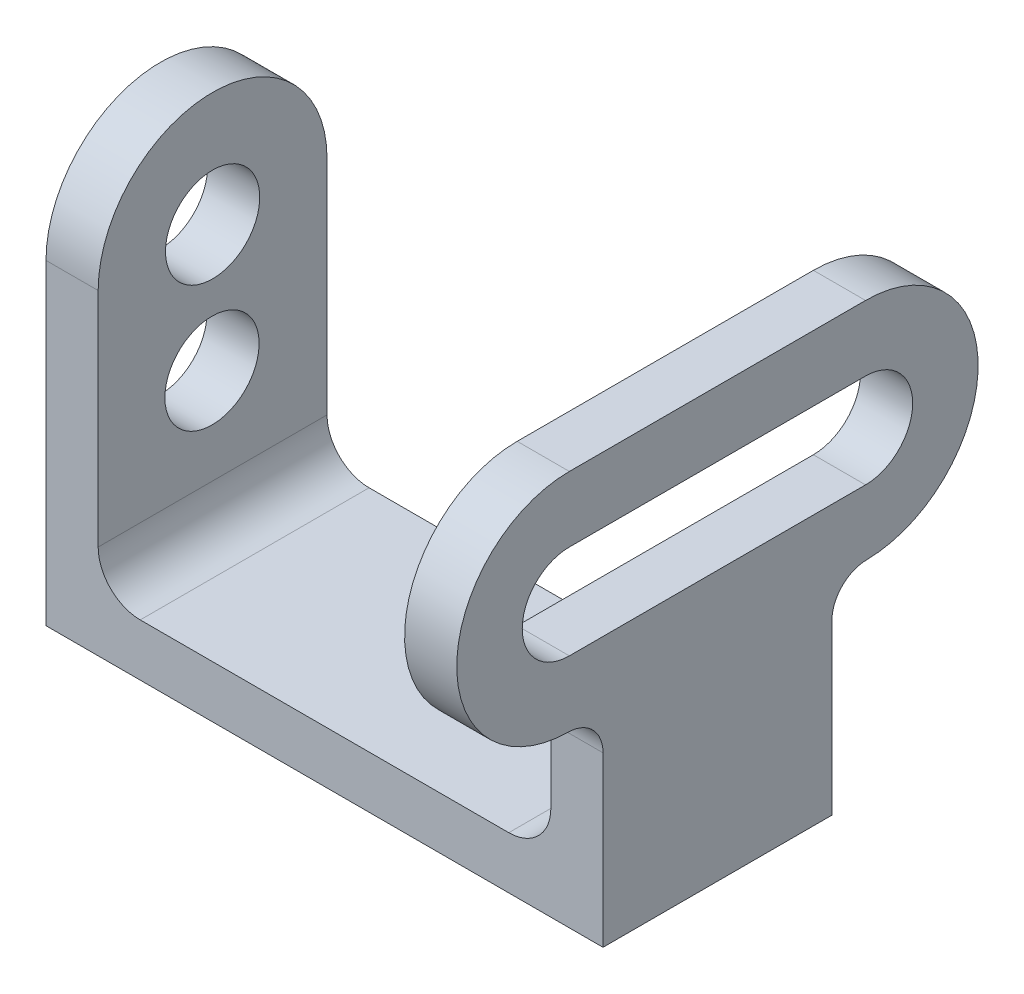
SolidWorks part; units mm, degrees
ref_plane "Front Plane" through (0, 0, 0) normal (0, 0, 1) x (1, 0, 0)
ref_plane "Top Plane" through (0, 0, 0) normal (0, 1, 0) x (1, 0, 0)
ref_plane "Right Plane" through (0, 0, 0) normal (1, 0, 0) x (0, 0, -1)
sketch "Sketch1" plane through (0, 0, 0) normal (0, 0, 1) x (1, 0, 0)
  line L0 (-66.2224, 33.9296) -> (-58.3484, 33.9296)
  line L1 (-58.3484, 33.9296) -> (-58.3484, -5.9484)
  line L2 (-58.3484, -5.9484) -> (9.9776, -5.9484)
  line L3 (9.9776, -5.9484) -> (9.9776, 33.9296)
  line L4 (9.9776, 33.9296) -> (17.8516, 33.9296)
  line L5 (17.8516, 33.9296) -> (17.8516, -13.8224)
  line L6 (17.8516, -13.8224) -> (-66.2224, -13.8224)
  line L7 (-66.2224, -13.8224) -> (-66.2224, 33.9296)
  dimension "D1" = 7.874
  dimension "D2" = 84.074
  dimension "D3" = 47.752
  dimension "D4" = 7.874
extrude "Boss-Extrude1" add sketch "Sketch1" against normal blind 34.544
sketch "Sketch2" plane through (-66.2224, 0, 0) normal (-1, 0, 0) x (0, 0, 1)
  line L0 (-34.544, 33.9296) -> (0, 33.9296) construction
  circle A0 centre (-17.272, 33.9296) radius 17.272
  circle A1 centre (-17.272, 33.9296) radius 7.112
  circle A2 centre (-17.1815, 14.8796) radius 7.112
  line M5 (0, 33.9296) -> (-34.544, 33.9296)
  dimension "D1" = 14.224
  dimension "D2" = 19.05
extrude "Cut-Extrude1" cut sketch "Sketch2" against normal up to surface (7.874 mm away) contours A1 M5 | A0 A2 | A0 A2 region at (-66.2224, 13.0217, -17.1727) region at (-66.2224, 19.1025, -17.2016) region at (-66.2224, 30.9112, -17.272) up to face at (-58.3484, 13.9906, -17.272)
extrude "Boss-Extrude2" add sketch "Sketch2<3>" against normal up to surface (7.874 mm away) contours A1 A0 M5 region at (-66.2224, 42.1404, -17.272) up to face at (-58.3484, 19.4516, -17.272)
sketch "Sketch2<3>" plane through (-66.2224, 0, 0) normal (-1, 0, 0) x (0, 0, 1) same geometry as "Sketch2"
sketch "Sketch3" plane through (17.8516, 0, 0) normal (1, 0, 0) x (0, 0, -1)
  line L0 (-5.08, 33.9296) -> (39.624, 33.9296) construction
  line L1 (34.544, 33.9296) -> (0, 33.9296) construction
  line L2 (-5.08, 50.9242) -> (39.624, 50.9242)
  line L3 (-5.08, 16.935) -> (39.624, 16.935)
  line L4 (-5.08, 33.9296) -> (39.624, 33.9296) construction
  line L5 (-5.08, 41.0416) -> (39.624, 41.0416)
  line L6 (-5.08, 26.8176) -> (39.624, 26.8176)
  line L7 (0, -13.8224) -> (0, 33.9296) construction
  line L8 (34.544, -13.8224) -> (34.544, 33.9296) construction
  arc A0 (-5.08, 50.9242) -> (-5.08, 16.935) centre (-5.08, 33.9296) ccw
  arc A1 (39.624, 16.935) -> (39.624, 50.9242) centre (39.624, 33.9296) ccw
  arc A2 (-5.08, 41.0416) -> (-5.08, 26.8176) centre (-5.08, 33.9296) ccw
  arc A3 (39.624, 26.8176) -> (39.624, 41.0416) centre (39.624, 33.9296) ccw
  arc A4 (0, 11.6024) -> (-5.334, 16.9364) centre (-5.334, 11.6024) ccw
  arc A5 (39.878, 16.9364) -> (34.544, 11.6024) centre (39.878, 11.6024) ccw
  point P4 (17.272, 33.9296)
  point P11 (17.272, 33.9296)
  line M1 (0, 33.9296) -> (0, -13.8224)
  line M3 (34.544, -13.8224) -> (34.544, 33.9296)
  line M4 (34.544, 33.9296) -> (0, 33.9296)
  dimension "D5" = 5.334
  dimension "D1" = 33.9893
  dimension "D2" = 44.704
  dimension "D3" = 14.224
  dimension "D4" = 44.704
extrude "Boss-Extrude3" add sketch "Sketch3" against normal up to surface (7.874 mm away) contours A4 L3 A0 M1 | A3 L6 L3 A1 L2 A0 A2 L5 M3 M1 | A5 A1 L3 M3 region at (17.8516, 50.067, -17.272) region at (17.8516, 15.7435, 1.1897) region at (17.8516, 15.7435, -35.7337) up to face at (9.9776, 13.9906, -17.272)
extrude "Cut-Extrude2" cut sketch "Sketch3<3>" against normal blind 34.544 contours L6 M1 M3 M4 region at (17.8516, 30.3736, -17.272)
sketch "Sketch3<3>" plane through (17.8516, 0, 0) normal (1, 0, 0) x (0, 0, -1) same geometry as "Sketch3"
fillet "Fillet1" radius 6.35 2 edges at (9.9776, -5.9484, -17.272) (-58.3484, -5.9484, -17.272)
